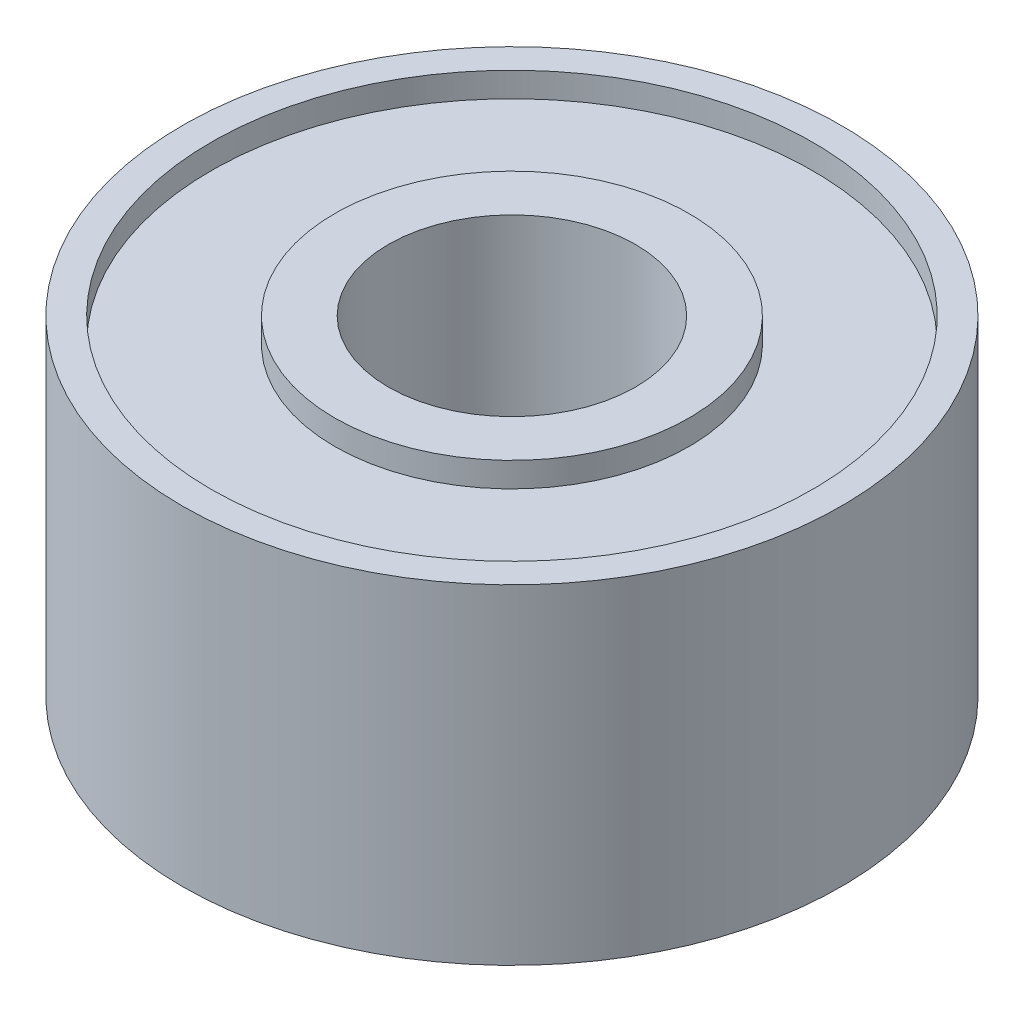
SolidWorks part; units mm, degrees
ref_plane "Front Plane" through (0, 0, 0) normal (0, 0, 1) x (1, 0, 0)
ref_plane "Top Plane" through (0, 0, 0) normal (0, 1, 0) x (1, 0, 0)
ref_plane "Right Plane" through (0, 0, 0) normal (1, 0, 0) x (0, 0, -1)
sketch "Sketch1" plane through (0, 0, 0) normal (0, 1, 0) x (1, 0, 0)
  circle A0 centre (0, 0) radius 4
  circle A1 centre (0, 0) radius 1.5
  dimension "D1" = 8
  dimension "D2" = 3
extrude "Base size" add sketch "Sketch1" along normal blind 4
sketch "Sketch2" plane through (0, 4, 0) normal (0, 1, 0) x (1, 0, 0)
  circle A0 centre (0, 0) radius 1.5 construction
  circle A1 centre (0, 0) radius 4
  circle A2 centre (0, 0) radius 4
  circle A3 centre (0, 0) radius 1.5
  circle A4 centre (0, 0) radius 2.15
  circle A5 centre (0, 0) radius 3.65
  dimension "D2" = 4.3
  dimension "D3" = 0.35
  dimension "D1" = 0
extrude "Bearing features" cut sketch "Sketch2" against normal blind 0.3 contours A5 A4 region at (-3.5468, 4, 0)
ref_plane "Center plane" through (0, 2, 0) normal (0, 1, 0) x (1, 0, 0)
mirror "Mirror1" about plane through (0, 2, 0) normal (0, 1, 0) of "Bearing features"
